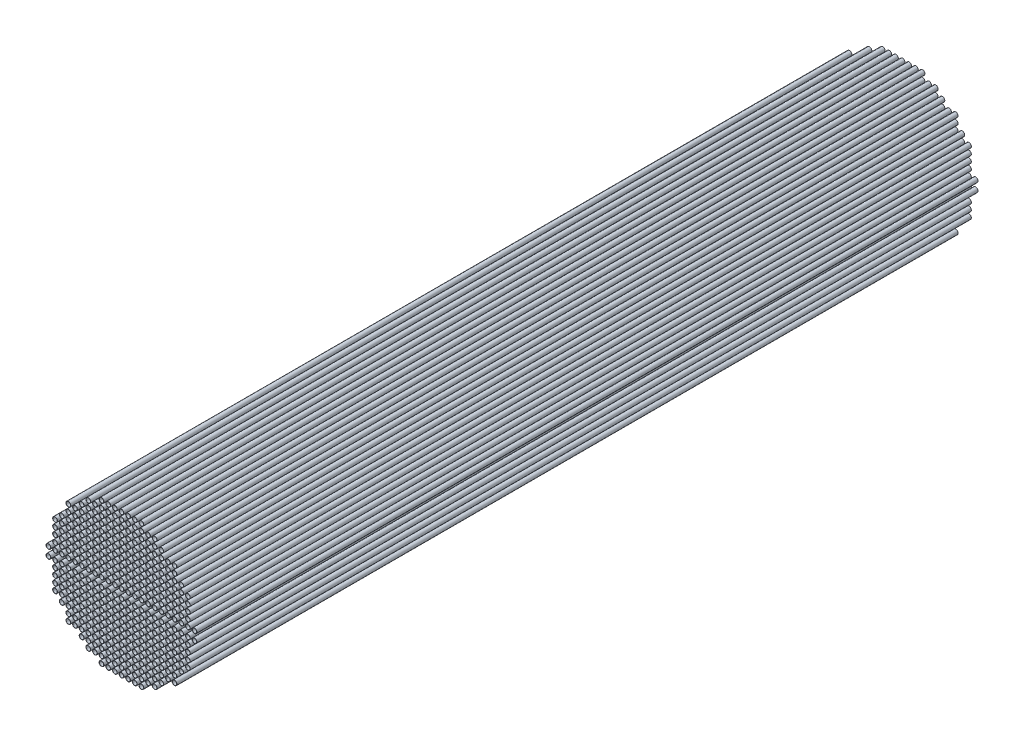
SolidWorks part; units mm, degrees
ref_plane "Plano frontal" through (0, 0, 0) normal (0, 0, 1) x (1, 0, 0)
ref_plane "Plano superior" through (0, 0, 0) normal (0, 1, 0) x (1, 0, 0)
ref_plane "Plano direito" through (0, 0, 0) normal (1, 0, 0) x (0, 0, -1)
sketch "Sketch2" plane through (0, 0, 0) normal (0, 0, 1) x (1, 0, 0)
  line L0 (-740, -13.1986) -> (-1154.1586, -13.1986) construction
  circle A0 centre (-454, -30.1144) radius 9.4918
  circle A1 centre (-454, -30.1144) radius 8.4918
  circle A2 centre (-480, -30.1144) radius 9.4918
  circle A3 centre (-480, -30.1144) radius 8.4918
  circle A4 centre (-506, -30.1144) radius 9.4918
  circle A5 centre (-506, -30.1144) radius 8.4918
  circle A6 centre (-532, -30.1144) radius 9.4918
  circle A7 centre (-532, -30.1144) radius 8.4918
  circle A8 centre (-558, -30.1144) radius 9.4918
  circle A9 centre (-558, -30.1144) radius 8.4918
  circle A10 centre (-584, -30.1144) radius 9.4918
  circle A11 centre (-584, -30.1144) radius 8.4918
  circle A12 centre (-610, -30.1144) radius 9.4918
  circle A13 centre (-610, -30.1144) radius 8.4918
  circle A14 centre (-636, -30.1144) radius 9.4918
  circle A15 centre (-636, -30.1144) radius 8.4918
  circle A16 centre (-662, -30.1144) radius 9.4918
  circle A17 centre (-662, -30.1144) radius 8.4918
  circle A18 centre (-688, -30.1144) radius 9.4918
  circle A19 centre (-688, -30.1144) radius 8.4918
  circle A20 centre (-714, -30.1144) radius 9.4918
  circle A21 centre (-714, -30.1144) radius 8.4918
  circle A22 centre (-740, -30.1144) radius 9.4918
  circle A23 centre (-740, -30.1144) radius 8.4918
  circle A24 centre (-766, -30.1144) radius 9.4918
  circle A25 centre (-766, -30.1144) radius 8.4918
  circle A26 centre (-792, -30.1144) radius 9.4918
  circle A27 centre (-792, -30.1144) radius 8.4918
  circle A28 centre (-818, -30.1144) radius 9.4918
  circle A29 centre (-818, -30.1144) radius 8.4918
  circle A30 centre (-844, -30.1144) radius 9.4918
  circle A31 centre (-844, -30.1144) radius 8.4918
  circle A32 centre (-870, -30.1144) radius 9.4918
  circle A33 centre (-870, -30.1144) radius 8.4918
  circle A34 centre (-896, -30.1144) radius 9.4918
  circle A35 centre (-896, -30.1144) radius 8.4918
  circle A36 centre (-922, -30.1144) radius 9.4918
  circle A37 centre (-922, -30.1144) radius 8.4918
  circle A38 centre (-948, -30.1144) radius 9.4918
  circle A39 centre (-948, -30.1144) radius 8.4918
  circle A40 centre (-974, -30.1144) radius 9.4918
  circle A41 centre (-974, -30.1144) radius 8.4918
  circle A42 centre (-1000, -30.1144) radius 9.4918
  circle A43 centre (-1000, -30.1144) radius 8.4918
  circle A44 centre (-1026, -30.1144) radius 9.4918
  circle A45 centre (-1026, -30.1144) radius 8.4918
  circle A46 centre (-480, -56.1144) radius 9.4918
  circle A47 centre (-480, -56.1144) radius 8.4918
  circle A48 centre (-506, -56.1144) radius 9.4918
  circle A49 centre (-506, -56.1144) radius 8.4918
  circle A50 centre (-532, -56.1144) radius 9.4918
  circle A51 centre (-532, -56.1144) radius 8.4918
  circle A52 centre (-558, -56.1144) radius 9.4918
  circle A53 centre (-558, -56.1144) radius 8.4918
  circle A54 centre (-584, -56.1144) radius 9.4918
  circle A55 centre (-584, -56.1144) radius 8.4918
  circle A56 centre (-610, -56.1144) radius 9.4918
  circle A57 centre (-610, -56.1144) radius 8.4918
  circle A58 centre (-636, -56.1144) radius 9.4918
  circle A59 centre (-636, -56.1144) radius 8.4918
  circle A60 centre (-662, -56.1144) radius 9.4918
  circle A61 centre (-662, -56.1144) radius 8.4918
  circle A62 centre (-688, -56.1144) radius 9.4918
  circle A63 centre (-688, -56.1144) radius 8.4918
  circle A64 centre (-714, -56.1144) radius 9.4918
  circle A65 centre (-714, -56.1144) radius 8.4918
  circle A66 centre (-740, -56.1144) radius 9.4918
  circle A67 centre (-740, -56.1144) radius 8.4918
  circle A68 centre (-766, -56.1144) radius 9.4918
  circle A69 centre (-766, -56.1144) radius 8.4918
  circle A70 centre (-792, -56.1144) radius 9.4918
  circle A71 centre (-792, -56.1144) radius 8.4918
  circle A72 centre (-818, -56.1144) radius 9.4918
  circle A73 centre (-818, -56.1144) radius 8.4918
  circle A74 centre (-844, -56.1144) radius 9.4918
  circle A75 centre (-844, -56.1144) radius 8.4918
  circle A76 centre (-870, -56.1144) radius 9.4918
  circle A77 centre (-870, -56.1144) radius 8.4918
  circle A78 centre (-896, -56.1144) radius 9.4918
  circle A79 centre (-896, -56.1144) radius 8.4918
  circle A80 centre (-922, -56.1144) radius 9.4918
  circle A81 centre (-922, -56.1144) radius 8.4918
  circle A82 centre (-948, -56.1144) radius 9.4918
  circle A83 centre (-948, -56.1144) radius 8.4918
  circle A84 centre (-974, -56.1144) radius 9.4918
  circle A85 centre (-974, -56.1144) radius 8.4918
  circle A86 centre (-1000, -56.1144) radius 9.4918
  circle A87 centre (-1000, -56.1144) radius 8.4918
  circle A88 centre (-818, 263.7171) radius 8.4918
  circle A89 centre (-818, 263.7171) radius 9.4918
  circle A90 centre (-480, -82.1144) radius 9.4918
  circle A91 centre (-480, -82.1144) radius 8.4918
  circle A92 centre (-506, -82.1144) radius 9.4918
  circle A93 centre (-506, -82.1144) radius 8.4918
  circle A94 centre (-532, -82.1144) radius 9.4918
  circle A95 centre (-532, -82.1144) radius 8.4918
  circle A96 centre (-558, -82.1144) radius 9.4918
  circle A97 centre (-558, -82.1144) radius 8.4918
  circle A98 centre (-584, -82.1144) radius 9.4918
  circle A99 centre (-584, -82.1144) radius 8.4918
  circle A100 centre (-610, -82.1144) radius 9.4918
  circle A101 centre (-610, -82.1144) radius 8.4918
  circle A102 centre (-636, -82.1144) radius 9.4918
  circle A103 centre (-636, -82.1144) radius 8.4918
  circle A104 centre (-662, -82.1144) radius 9.4918
  circle A105 centre (-662, -82.1144) radius 8.4918
  circle A106 centre (-688, -82.1144) radius 9.4918
  circle A107 centre (-688, -82.1144) radius 8.4918
  circle A108 centre (-714, -82.1144) radius 9.4918
  circle A109 centre (-714, -82.1144) radius 8.4918
  circle A110 centre (-740, -82.1144) radius 9.4918
  circle A111 centre (-740, -82.1144) radius 8.4918
  circle A112 centre (-766, -82.1144) radius 9.4918
  circle A113 centre (-766, -82.1144) radius 8.4918
  circle A114 centre (-792, -82.1144) radius 9.4918
  circle A115 centre (-792, -82.1144) radius 8.4918
  circle A116 centre (-818, -82.1144) radius 9.4918
  circle A117 centre (-818, -82.1144) radius 8.4918
  circle A118 centre (-844, -82.1144) radius 9.4918
  circle A119 centre (-844, -82.1144) radius 8.4918
  circle A120 centre (-870, -82.1144) radius 9.4918
  circle A121 centre (-870, -82.1144) radius 8.4918
  circle A122 centre (-896, -82.1144) radius 9.4918
  circle A123 centre (-896, -82.1144) radius 8.4918
  circle A124 centre (-922, -82.1144) radius 9.4918
  circle A125 centre (-922, -82.1144) radius 8.4918
  circle A126 centre (-948, -82.1144) radius 9.4918
  circle A127 centre (-948, -82.1144) radius 8.4918
  circle A128 centre (-974, -82.1144) radius 9.4918
  circle A129 centre (-974, -82.1144) radius 8.4918
  circle A130 centre (-1000, -82.1144) radius 9.4918
  circle A131 centre (-1000, -82.1144) radius 8.4918
  circle A132 centre (-792, 263.7171) radius 8.4918
  circle A133 centre (-792, 263.7171) radius 9.4918
  circle A134 centre (-480, -108.1144) radius 9.4918
  circle A135 centre (-480, -108.1144) radius 8.4918
  circle A136 centre (-506, -108.1144) radius 9.4918
  circle A137 centre (-506, -108.1144) radius 8.4918
  circle A138 centre (-532, -108.1144) radius 9.4918
  circle A139 centre (-532, -108.1144) radius 8.4918
  circle A140 centre (-558, -108.1144) radius 9.4918
  circle A141 centre (-558, -108.1144) radius 8.4918
  circle A142 centre (-584, -108.1144) radius 9.4918
  circle A143 centre (-584, -108.1144) radius 8.4918
  circle A144 centre (-610, -108.1144) radius 9.4918
  circle A145 centre (-610, -108.1144) radius 8.4918
  circle A146 centre (-636, -108.1144) radius 9.4918
  circle A147 centre (-636, -108.1144) radius 8.4918
  circle A148 centre (-662, -108.1144) radius 9.4918
  circle A149 centre (-662, -108.1144) radius 8.4918
  circle A150 centre (-688, -108.1144) radius 9.4918
  circle A151 centre (-688, -108.1144) radius 8.4918
  circle A152 centre (-714, -108.1144) radius 9.4918
  circle A153 centre (-714, -108.1144) radius 8.4918
  circle A154 centre (-740, -108.1144) radius 9.4918
  circle A155 centre (-740, -108.1144) radius 8.4918
  circle A156 centre (-766, -108.1144) radius 9.4918
  circle A157 centre (-766, -108.1144) radius 8.4918
  circle A158 centre (-792, -108.1144) radius 9.4918
  circle A159 centre (-792, -108.1144) radius 8.4918
  circle A160 centre (-818, -108.1144) radius 9.4918
  circle A161 centre (-818, -108.1144) radius 8.4918
  circle A162 centre (-844, -108.1144) radius 9.4918
  circle A163 centre (-844, -108.1144) radius 8.4918
  circle A164 centre (-870, -108.1144) radius 9.4918
  circle A165 centre (-870, -108.1144) radius 8.4918
  circle A166 centre (-896, -108.1144) radius 9.4918
  circle A167 centre (-896, -108.1144) radius 8.4918
  circle A168 centre (-922, -108.1144) radius 9.4918
  circle A169 centre (-922, -108.1144) radius 8.4918
  circle A170 centre (-948, -108.1144) radius 9.4918
  circle A171 centre (-948, -108.1144) radius 8.4918
  circle A172 centre (-974, -108.1144) radius 9.4918
  circle A173 centre (-974, -108.1144) radius 8.4918
  circle A174 centre (-1000, -108.1144) radius 9.4918
  circle A175 centre (-1000, -108.1144) radius 8.4918
  circle A176 centre (-766, 263.7171) radius 8.4918
  circle A177 centre (-766, 263.7171) radius 9.4918
  circle A178 centre (-480, -134.1144) radius 9.4918
  circle A179 centre (-480, -134.1144) radius 8.4918
  circle A180 centre (-506, -134.1144) radius 9.4918
  circle A181 centre (-506, -134.1144) radius 8.4918
  circle A182 centre (-532, -134.1144) radius 9.4918
  circle A183 centre (-532, -134.1144) radius 8.4918
  circle A184 centre (-558, -134.1144) radius 9.4918
  circle A185 centre (-558, -134.1144) radius 8.4918
  circle A186 centre (-584, -134.1144) radius 9.4918
  circle A187 centre (-584, -134.1144) radius 8.4918
  circle A188 centre (-610, -134.1144) radius 9.4918
  circle A189 centre (-610, -134.1144) radius 8.4918
  circle A190 centre (-636, -134.1144) radius 9.4918
  circle A191 centre (-636, -134.1144) radius 8.4918
  circle A192 centre (-662, -134.1144) radius 9.4918
  circle A193 centre (-662, -134.1144) radius 8.4918
  circle A194 centre (-688, -134.1144) radius 9.4918
  circle A195 centre (-688, -134.1144) radius 8.4918
  circle A196 centre (-714, -134.1144) radius 9.4918
  circle A197 centre (-714, -134.1144) radius 8.4918
  circle A198 centre (-740, -134.1144) radius 9.4918
  circle A199 centre (-740, -134.1144) radius 8.4918
  circle A200 centre (-766, -134.1144) radius 9.4918
  circle A201 centre (-766, -134.1144) radius 8.4918
  circle A202 centre (-792, -134.1144) radius 9.4918
  circle A203 centre (-792, -134.1144) radius 8.4918
  circle A204 centre (-818, -134.1144) radius 9.4918
  circle A205 centre (-818, -134.1144) radius 8.4918
  circle A206 centre (-844, -134.1144) radius 9.4918
  circle A207 centre (-844, -134.1144) radius 8.4918
  circle A208 centre (-870, -134.1144) radius 9.4918
  circle A209 centre (-870, -134.1144) radius 8.4918
  circle A210 centre (-896, -134.1144) radius 9.4918
  circle A211 centre (-896, -134.1144) radius 8.4918
  circle A212 centre (-922, -134.1144) radius 9.4918
  circle A213 centre (-922, -134.1144) radius 8.4918
  circle A214 centre (-948, -134.1144) radius 9.4918
  circle A215 centre (-948, -134.1144) radius 8.4918
  circle A216 centre (-974, -134.1144) radius 9.4918
  circle A217 centre (-974, -134.1144) radius 8.4918
  circle A218 centre (-1000, -134.1144) radius 9.4918
  circle A219 centre (-1000, -134.1144) radius 8.4918
  circle A220 centre (-740, 263.7171) radius 8.4918
  circle A221 centre (-740, 263.7171) radius 9.4918
  circle A222 centre (-714, 263.7171) radius 8.4918
  circle A223 centre (-714, 263.7171) radius 9.4918
  circle A224 centre (-506, -160.1144) radius 9.4918
  circle A225 centre (-506, -160.1144) radius 8.4918
  circle A226 centre (-532, -160.1144) radius 9.4918
  circle A227 centre (-532, -160.1144) radius 8.4918
  circle A228 centre (-558, -160.1144) radius 9.4918
  circle A229 centre (-558, -160.1144) radius 8.4918
  circle A230 centre (-584, -160.1144) radius 9.4918
  circle A231 centre (-584, -160.1144) radius 8.4918
  circle A232 centre (-610, -160.1144) radius 9.4918
  circle A233 centre (-610, -160.1144) radius 8.4918
  circle A234 centre (-636, -160.1144) radius 9.4918
  circle A235 centre (-636, -160.1144) radius 8.4918
  circle A236 centre (-662, -160.1144) radius 9.4918
  circle A237 centre (-662, -160.1144) radius 8.4918
  circle A238 centre (-688, -160.1144) radius 9.4918
  circle A239 centre (-688, -160.1144) radius 8.4918
  circle A240 centre (-714, -160.1144) radius 9.4918
  circle A241 centre (-714, -160.1144) radius 8.4918
  circle A242 centre (-740, -160.1144) radius 9.4918
  circle A243 centre (-740, -160.1144) radius 8.4918
  circle A244 centre (-766, -160.1144) radius 9.4918
  circle A245 centre (-766, -160.1144) radius 8.4918
  circle A246 centre (-792, -160.1144) radius 9.4918
  circle A247 centre (-792, -160.1144) radius 8.4918
  circle A248 centre (-818, -160.1144) radius 9.4918
  circle A249 centre (-818, -160.1144) radius 8.4918
  circle A250 centre (-844, -160.1144) radius 9.4918
  circle A251 centre (-844, -160.1144) radius 8.4918
  circle A252 centre (-870, -160.1144) radius 9.4918
  circle A253 centre (-870, -160.1144) radius 8.4918
  circle A254 centre (-896, -160.1144) radius 9.4918
  circle A255 centre (-896, -160.1144) radius 8.4918
  circle A256 centre (-922, -160.1144) radius 9.4918
  circle A257 centre (-922, -160.1144) radius 8.4918
  circle A258 centre (-948, -160.1144) radius 9.4918
  circle A259 centre (-948, -160.1144) radius 8.4918
  circle A260 centre (-974, -160.1144) radius 9.4918
  circle A261 centre (-974, -160.1144) radius 8.4918
  circle A262 centre (-688, 263.7171) radius 8.4918
  circle A263 centre (-688, 263.7171) radius 9.4918
  circle A264 centre (-662, 263.7171) radius 8.4918
  circle A265 centre (-662, 263.7171) radius 9.4918
  circle A266 centre (-870, 237.7171) radius 8.4918
  circle A267 centre (-870, 237.7171) radius 9.4918
  circle A268 centre (-844, 237.7171) radius 8.4918
  circle A269 centre (-844, 237.7171) radius 9.4918
  circle A270 centre (-532, -186.1144) radius 9.4918
  circle A271 centre (-532, -186.1144) radius 8.4918
  circle A272 centre (-558, -186.1144) radius 9.4918
  circle A273 centre (-558, -186.1144) radius 8.4918
  circle A274 centre (-584, -186.1144) radius 9.4918
  circle A275 centre (-584, -186.1144) radius 8.4918
  circle A276 centre (-610, -186.1144) radius 9.4918
  circle A277 centre (-610, -186.1144) radius 8.4918
  circle A278 centre (-636, -186.1144) radius 9.4918
  circle A279 centre (-636, -186.1144) radius 8.4918
  circle A280 centre (-662, -186.1144) radius 9.4918
  circle A281 centre (-662, -186.1144) radius 8.4918
  circle A282 centre (-688, -186.1144) radius 9.4918
  circle A283 centre (-688, -186.1144) radius 8.4918
  circle A284 centre (-714, -186.1144) radius 9.4918
  circle A285 centre (-714, -186.1144) radius 8.4918
  circle A286 centre (-740, -186.1144) radius 9.4918
  circle A287 centre (-740, -186.1144) radius 8.4918
  circle A288 centre (-766, -186.1144) radius 9.4918
  circle A289 centre (-766, -186.1144) radius 8.4918
  circle A290 centre (-792, -186.1144) radius 9.4918
  circle A291 centre (-792, -186.1144) radius 8.4918
  circle A292 centre (-818, -186.1144) radius 9.4918
  circle A293 centre (-818, -186.1144) radius 8.4918
  circle A294 centre (-844, -186.1144) radius 9.4918
  circle A295 centre (-844, -186.1144) radius 8.4918
  circle A296 centre (-870, -186.1144) radius 9.4918
  circle A297 centre (-870, -186.1144) radius 8.4918
  circle A298 centre (-896, -186.1144) radius 9.4918
  circle A299 centre (-896, -186.1144) radius 8.4918
  circle A300 centre (-922, -186.1144) radius 9.4918
  circle A301 centre (-922, -186.1144) radius 8.4918
  circle A302 centre (-948, -186.1144) radius 9.4918
  circle A303 centre (-948, -186.1144) radius 8.4918
  circle A304 centre (-818, 237.7171) radius 8.4918
  circle A305 centre (-818, 237.7171) radius 9.4918
  circle A306 centre (-792, 237.7171) radius 8.4918
  circle A307 centre (-792, 237.7171) radius 9.4918
  circle A308 centre (-766, 237.7171) radius 8.4918
  circle A309 centre (-766, 237.7171) radius 9.4918
  circle A310 centre (-740, 237.7171) radius 8.4918
  circle A311 centre (-740, 237.7171) radius 9.4918
  circle A312 centre (-714, 237.7171) radius 8.4918
  circle A313 centre (-714, 237.7171) radius 9.4918
  circle A314 centre (-532, -212.1144) radius 9.4918
  circle A315 centre (-532, -212.1144) radius 8.4918
  circle A316 centre (-558, -212.1144) radius 9.4918
  circle A317 centre (-558, -212.1144) radius 8.4918
  circle A318 centre (-584, -212.1144) radius 9.4918
  circle A319 centre (-584, -212.1144) radius 8.4918
  circle A320 centre (-610, -212.1144) radius 9.4918
  circle A321 centre (-610, -212.1144) radius 8.4918
  circle A322 centre (-636, -212.1144) radius 9.4918
  circle A323 centre (-636, -212.1144) radius 8.4918
  circle A324 centre (-662, -212.1144) radius 9.4918
  circle A325 centre (-662, -212.1144) radius 8.4918
  circle A326 centre (-688, -212.1144) radius 9.4918
  circle A327 centre (-688, -212.1144) radius 8.4918
  circle A328 centre (-714, -212.1144) radius 9.4918
  circle A329 centre (-714, -212.1144) radius 8.4918
  circle A330 centre (-740, -212.1144) radius 9.4918
  circle A331 centre (-740, -212.1144) radius 8.4918
  circle A332 centre (-766, -212.1144) radius 9.4918
  circle A333 centre (-766, -212.1144) radius 8.4918
  circle A334 centre (-792, -212.1144) radius 9.4918
  circle A335 centre (-792, -212.1144) radius 8.4918
  circle A336 centre (-818, -212.1144) radius 9.4918
  circle A337 centre (-818, -212.1144) radius 8.4918
  circle A338 centre (-844, -212.1144) radius 9.4918
  circle A339 centre (-844, -212.1144) radius 8.4918
  circle A340 centre (-870, -212.1144) radius 9.4918
  circle A341 centre (-870, -212.1144) radius 8.4918
  circle A342 centre (-896, -212.1144) radius 9.4918
  circle A343 centre (-896, -212.1144) radius 8.4918
  circle A344 centre (-922, -212.1144) radius 9.4918
  circle A345 centre (-922, -212.1144) radius 8.4918
  circle A346 centre (-948, -212.1144) radius 9.4918
  circle A347 centre (-948, -212.1144) radius 8.4918
  circle A348 centre (-688, 237.7171) radius 8.4918
  circle A349 centre (-688, 237.7171) radius 9.4918
  circle A350 centre (-662, 237.7171) radius 8.4918
  circle A351 centre (-662, 237.7171) radius 9.4918
  circle A352 centre (-636, 237.7171) radius 8.4918
  circle A353 centre (-636, 237.7171) radius 9.4918
  circle A354 centre (-610, 237.7171) radius 8.4918
  circle A355 centre (-610, 237.7171) radius 9.4918
  circle A356 centre (-896, 211.7171) radius 8.4918
  circle A357 centre (-896, 211.7171) radius 9.4918
  circle A358 centre (-870, 211.7171) radius 8.4918
  circle A359 centre (-870, 211.7171) radius 9.4918
  circle A360 centre (-844, 211.7171) radius 8.4918
  circle A361 centre (-844, 211.7171) radius 9.4918
  circle A362 centre (-584, -238.1144) radius 9.4918
  circle A363 centre (-584, -238.1144) radius 8.4918
  circle A364 centre (-610, -238.1144) radius 9.4918
  circle A365 centre (-610, -238.1144) radius 8.4918
  circle A366 centre (-636, -238.1144) radius 9.4918
  circle A367 centre (-636, -238.1144) radius 8.4918
  circle A368 centre (-662, -238.1144) radius 9.4918
  circle A369 centre (-662, -238.1144) radius 8.4918
  circle A370 centre (-688, -238.1144) radius 9.4918
  circle A371 centre (-688, -238.1144) radius 8.4918
  circle A372 centre (-714, -238.1144) radius 9.4918
  circle A373 centre (-714, -238.1144) radius 8.4918
  circle A374 centre (-740, -238.1144) radius 9.4918
  circle A375 centre (-740, -238.1144) radius 8.4918
  circle A376 centre (-766, -238.1144) radius 9.4918
  circle A377 centre (-766, -238.1144) radius 8.4918
  circle A378 centre (-792, -238.1144) radius 9.4918
  circle A379 centre (-792, -238.1144) radius 8.4918
  circle A380 centre (-818, -238.1144) radius 9.4918
  circle A381 centre (-818, -238.1144) radius 8.4918
  circle A382 centre (-844, -238.1144) radius 9.4918
  circle A383 centre (-844, -238.1144) radius 8.4918
  circle A384 centre (-870, -238.1144) radius 9.4918
  circle A385 centre (-870, -238.1144) radius 8.4918
  circle A386 centre (-896, -238.1144) radius 9.4918
  circle A387 centre (-896, -238.1144) radius 8.4918
  circle A388 centre (-818, 211.7171) radius 8.4918
  circle A389 centre (-818, 211.7171) radius 9.4918
  circle A390 centre (-792, 211.7171) radius 8.4918
  circle A391 centre (-792, 211.7171) radius 9.4918
  circle A392 centre (-766, 211.7171) radius 8.4918
  circle A393 centre (-766, 211.7171) radius 9.4918
  circle A394 centre (-740, 211.7171) radius 8.4918
  circle A395 centre (-740, 211.7171) radius 9.4918
  circle A396 centre (-714, 211.7171) radius 8.4918
  circle A397 centre (-714, 211.7171) radius 9.4918
  circle A398 centre (-688, 211.7171) radius 8.4918
  circle A399 centre (-688, 211.7171) radius 9.4918
  circle A400 centre (-662, 211.7171) radius 8.4918
  circle A401 centre (-662, 211.7171) radius 9.4918
  circle A402 centre (-636, 211.7171) radius 8.4918
  circle A403 centre (-636, 211.7171) radius 9.4918
  circle A404 centre (-610, 211.7171) radius 8.4918
  circle A405 centre (-610, 211.7171) radius 9.4918
  circle A406 centre (-584, 211.7171) radius 8.4918
  circle A407 centre (-584, 211.7171) radius 9.4918
  circle A408 centre (-610, -264.1144) radius 9.4918
  circle A409 centre (-610, -264.1144) radius 8.4918
  circle A410 centre (-636, -264.1144) radius 9.4918
  circle A411 centre (-636, -264.1144) radius 8.4918
  circle A412 centre (-662, -264.1144) radius 9.4918
  circle A413 centre (-662, -264.1144) radius 8.4918
  circle A414 centre (-688, -264.1144) radius 9.4918
  circle A415 centre (-688, -264.1144) radius 8.4918
  circle A416 centre (-714, -264.1144) radius 9.4918
  circle A417 centre (-714, -264.1144) radius 8.4918
  circle A418 centre (-740, -264.1144) radius 9.4918
  circle A419 centre (-740, -264.1144) radius 8.4918
  circle A420 centre (-766, -264.1144) radius 9.4918
  circle A421 centre (-766, -264.1144) radius 8.4918
  circle A422 centre (-792, -264.1144) radius 9.4918
  circle A423 centre (-792, -264.1144) radius 8.4918
  circle A424 centre (-818, -264.1144) radius 9.4918
  circle A425 centre (-818, -264.1144) radius 8.4918
  circle A426 centre (-844, -264.1144) radius 9.4918
  circle A427 centre (-844, -264.1144) radius 8.4918
  circle A428 centre (-870, -264.1144) radius 9.4918
  circle A429 centre (-870, -264.1144) radius 8.4918
  circle A430 centre (-948, 185.7171) radius 8.4918
  circle A431 centre (-948, 185.7171) radius 9.4918
  circle A432 centre (-922, 185.7171) radius 8.4918
  circle A433 centre (-922, 185.7171) radius 9.4918
  circle A434 centre (-896, 185.7171) radius 8.4918
  circle A435 centre (-896, 185.7171) radius 9.4918
  circle A436 centre (-870, 185.7171) radius 8.4918
  circle A437 centre (-870, 185.7171) radius 9.4918
  circle A438 centre (-844, 185.7171) radius 8.4918
  circle A439 centre (-844, 185.7171) radius 9.4918
  circle A440 centre (-818, 185.7171) radius 8.4918
  circle A441 centre (-818, 185.7171) radius 9.4918
  circle A442 centre (-792, 185.7171) radius 8.4918
  circle A443 centre (-792, 185.7171) radius 9.4918
  circle A444 centre (-766, 185.7171) radius 8.4918
  circle A445 centre (-766, 185.7171) radius 9.4918
  circle A446 centre (-740, 185.7171) radius 8.4918
  circle A447 centre (-740, 185.7171) radius 9.4918
  circle A448 centre (-714, 185.7171) radius 8.4918
  circle A449 centre (-714, 185.7171) radius 9.4918
  circle A450 centre (-688, 185.7171) radius 8.4918
  circle A451 centre (-688, 185.7171) radius 9.4918
  circle A452 centre (-662, 185.7171) radius 8.4918
  circle A453 centre (-662, 185.7171) radius 9.4918
  circle A454 centre (-636, 185.7171) radius 8.4918
  circle A455 centre (-636, 185.7171) radius 9.4918
  circle A456 centre (-662, -290.1144) radius 9.4918
  circle A457 centre (-662, -290.1144) radius 8.4918
  circle A458 centre (-688, -290.1144) radius 9.4918
  circle A459 centre (-688, -290.1144) radius 8.4918
  circle A460 centre (-714, -290.1144) radius 9.4918
  circle A461 centre (-714, -290.1144) radius 8.4918
  circle A462 centre (-740, -290.1144) radius 9.4918
  circle A463 centre (-740, -290.1144) radius 8.4918
  circle A464 centre (-766, -290.1144) radius 9.4918
  circle A465 centre (-766, -290.1144) radius 8.4918
  circle A466 centre (-792, -290.1144) radius 9.4918
  circle A467 centre (-792, -290.1144) radius 8.4918
  circle A468 centre (-818, -290.1144) radius 9.4918
  circle A469 centre (-818, -290.1144) radius 8.4918
  circle A470 centre (-610, 185.7171) radius 8.4918
  circle A471 centre (-610, 185.7171) radius 9.4918
  circle A472 centre (-584, 185.7171) radius 8.4918
  circle A473 centre (-584, 185.7171) radius 9.4918
  circle A474 centre (-558, 185.7171) radius 8.4918
  circle A475 centre (-558, 185.7171) radius 9.4918
  circle A476 centre (-532, 185.7171) radius 8.4918
  circle A477 centre (-532, 185.7171) radius 9.4918
  circle A478 centre (-948, 159.7171) radius 8.4918
  circle A479 centre (-948, 159.7171) radius 9.4918
  circle A480 centre (-922, 159.7171) radius 8.4918
  circle A481 centre (-922, 159.7171) radius 9.4918
  circle A482 centre (-896, 159.7171) radius 8.4918
  circle A483 centre (-896, 159.7171) radius 9.4918
  circle A484 centre (-870, 159.7171) radius 8.4918
  circle A485 centre (-870, 159.7171) radius 9.4918
  circle A486 centre (-844, 159.7171) radius 8.4918
  circle A487 centre (-844, 159.7171) radius 9.4918
  circle A488 centre (-818, 159.7171) radius 8.4918
  circle A489 centre (-818, 159.7171) radius 9.4918
  circle A490 centre (-792, 159.7171) radius 8.4918
  circle A491 centre (-792, 159.7171) radius 9.4918
  circle A492 centre (-766, 159.7171) radius 8.4918
  circle A493 centre (-766, 159.7171) radius 9.4918
  circle A494 centre (-740, 159.7171) radius 8.4918
  circle A495 centre (-740, 159.7171) radius 9.4918
  circle A496 centre (-714, 159.7171) radius 8.4918
  circle A497 centre (-714, 159.7171) radius 9.4918
  circle A498 centre (-688, 159.7171) radius 8.4918
  circle A499 centre (-688, 159.7171) radius 9.4918
  circle A500 centre (-662, 159.7171) radius 8.4918
  circle A501 centre (-662, 159.7171) radius 9.4918
  circle A502 centre (-636, 159.7171) radius 8.4918
  circle A503 centre (-636, 159.7171) radius 9.4918
  circle A504 centre (-610, 159.7171) radius 8.4918
  circle A505 centre (-610, 159.7171) radius 9.4918
  circle A506 centre (-896, -290.1144) radius 9.4918 [skipped]
  circle A507 centre (-896, -290.1144) radius 8.4918 [skipped]
  circle A508 centre (-922, -290.1144) radius 9.4918 [skipped]
  circle A509 centre (-922, -290.1144) radius 8.4918 [skipped]
  circle A510 centre (-948, -290.1144) radius 9.4918 [skipped]
  circle A511 centre (-948, -290.1144) radius 8.4918 [skipped]
  circle A512 centre (-974, -290.1144) radius 9.4918 [skipped]
  circle A513 centre (-974, -290.1144) radius 8.4918 [skipped]
  circle A514 centre (-1000, -290.1144) radius 9.4918 [skipped]
  circle A515 centre (-1000, -290.1144) radius 8.4918 [skipped]
  circle A516 centre (-1026, -290.1144) radius 9.4918 [skipped]
  circle A517 centre (-1026, -290.1144) radius 8.4918 [skipped]
  circle A518 centre (-844, -290.1144) radius 9.4918 [skipped]
  circle A519 centre (-844, -290.1144) radius 8.4918 [skipped]
  circle A520 centre (-870, -290.1144) radius 9.4918 [skipped]
  circle A521 centre (-870, -290.1144) radius 8.4918 [skipped]
  circle A522 centre (-896, -264.1144) radius 9.4918 [skipped]
  circle A523 centre (-896, -264.1144) radius 8.4918 [skipped]
  circle A524 centre (-922, -264.1144) radius 9.4918 [skipped]
  circle A525 centre (-922, -264.1144) radius 8.4918 [skipped]
  circle A526 centre (-948, -264.1144) radius 9.4918 [skipped]
  circle A527 centre (-948, -264.1144) radius 8.4918 [skipped]
  circle A528 centre (-974, -264.1144) radius 9.4918 [skipped]
  circle A529 centre (-974, -264.1144) radius 8.4918 [skipped]
  circle A530 centre (-1000, -264.1144) radius 9.4918 [skipped]
  circle A531 centre (-1000, -264.1144) radius 8.4918 [skipped]
  circle A532 centre (-1026, -264.1144) radius 9.4918 [skipped]
  circle A533 centre (-1026, -264.1144) radius 8.4918 [skipped]
  circle A534 centre (-922, -238.1144) radius 9.4918 [skipped]
  circle A535 centre (-922, -238.1144) radius 8.4918 [skipped]
  circle A536 centre (-948, -238.1144) radius 9.4918 [skipped]
  circle A537 centre (-948, -238.1144) radius 8.4918 [skipped]
  circle A538 centre (-974, -238.1144) radius 9.4918 [skipped]
  circle A539 centre (-974, -238.1144) radius 8.4918 [skipped]
  circle A540 centre (-1000, -238.1144) radius 9.4918 [skipped]
  circle A541 centre (-1000, -238.1144) radius 8.4918 [skipped]
  circle A542 centre (-1026, -238.1144) radius 9.4918 [skipped]
  circle A543 centre (-1026, -238.1144) radius 8.4918 [skipped]
  circle A544 centre (-974, -186.1144) radius 9.4918 [skipped]
  circle A545 centre (-974, -186.1144) radius 8.4918 [skipped]
  circle A546 centre (-1000, -186.1144) radius 9.4918 [skipped]
  circle A547 centre (-1000, -186.1144) radius 8.4918 [skipped]
  circle A548 centre (-1026, -186.1144) radius 9.4918 [skipped]
  circle A549 centre (-1026, -186.1144) radius 8.4918 [skipped]
  circle A550 centre (-974, -212.1144) radius 9.4918 [skipped]
  circle A551 centre (-974, -212.1144) radius 8.4918 [skipped]
  circle A552 centre (-1000, -212.1144) radius 9.4918 [skipped]
  circle A553 centre (-1000, -212.1144) radius 8.4918 [skipped]
  circle A554 centre (-1026, -212.1144) radius 9.4918 [skipped]
  circle A555 centre (-1026, -212.1144) radius 8.4918 [skipped]
  circle A556 centre (-1000, -160.1144) radius 9.4918 [skipped]
  circle A557 centre (-1000, -160.1144) radius 8.4918 [skipped]
  circle A558 centre (-1026, -160.1144) radius 9.4918 [skipped]
  circle A559 centre (-1026, -160.1144) radius 8.4918 [skipped]
  circle A560 centre (-1026, -56.1144) radius 9.4918 [skipped]
  circle A561 centre (-1026, -56.1144) radius 8.4918 [skipped]
  circle A562 centre (-1026, -82.1144) radius 9.4918 [skipped]
  circle A563 centre (-1026, -82.1144) radius 8.4918 [skipped]
  circle A564 centre (-1026, -108.1144) radius 9.4918 [skipped]
  circle A565 centre (-1026, -108.1144) radius 8.4918 [skipped]
  circle A566 centre (-1026, -134.1144) radius 9.4918 [skipped]
  circle A567 centre (-1026, -134.1144) radius 8.4918 [skipped]
  circle A568 centre (-480, -160.1144) radius 9.4918 [skipped]
  circle A569 centre (-480, -160.1144) radius 8.4918 [skipped]
  circle A570 centre (-480, -186.1144) radius 9.4918 [skipped]
  circle A571 centre (-480, -186.1144) radius 8.4918 [skipped]
  circle A572 centre (-480, -212.1144) radius 9.4918 [skipped]
  circle A573 centre (-480, -212.1144) radius 8.4918 [skipped]
  circle A574 centre (-480, -238.1144) radius 9.4918 [skipped]
  circle A575 centre (-480, -238.1144) radius 8.4918 [skipped]
  circle A576 centre (-480, -264.1144) radius 9.4918 [skipped]
  circle A577 centre (-480, -264.1144) radius 8.4918 [skipped]
  circle A578 centre (-480, -290.1144) radius 9.4918 [skipped]
  circle A579 centre (-480, -290.1144) radius 8.4918 [skipped]
  circle A580 centre (-454, -160.1144) radius 9.4918 [skipped]
  circle A581 centre (-454, -160.1144) radius 8.4918 [skipped]
  circle A582 centre (-454, -186.1144) radius 9.4918 [skipped]
  circle A583 centre (-454, -186.1144) radius 8.4918 [skipped]
  circle A584 centre (-454, -212.1144) radius 9.4918 [skipped]
  circle A585 centre (-454, -212.1144) radius 8.4918 [skipped]
  circle A586 centre (-454, -238.1144) radius 9.4918 [skipped]
  circle A587 centre (-454, -238.1144) radius 8.4918 [skipped]
  circle A588 centre (-454, -264.1144) radius 9.4918 [skipped]
  circle A589 centre (-454, -264.1144) radius 8.4918 [skipped]
  circle A590 centre (-454, -290.1144) radius 9.4918 [skipped]
  circle A591 centre (-454, -290.1144) radius 8.4918 [skipped]
  circle A592 centre (-506, -186.1144) radius 9.4918 [skipped]
  circle A593 centre (-506, -186.1144) radius 8.4918 [skipped]
  circle A594 centre (-506, -212.1144) radius 9.4918 [skipped]
  circle A595 centre (-506, -212.1144) radius 8.4918 [skipped]
  circle A596 centre (-506, -238.1144) radius 9.4918 [skipped]
  circle A597 centre (-506, -238.1144) radius 8.4918 [skipped]
  circle A598 centre (-506, -264.1144) radius 9.4918 [skipped]
  circle A599 centre (-506, -264.1144) radius 8.4918 [skipped]
  circle A600 centre (-506, -290.1144) radius 9.4918 [skipped]
  circle A601 centre (-506, -290.1144) radius 8.4918 [skipped]
  circle A602 centre (-532, -238.1144) radius 9.4918 [skipped]
  circle A603 centre (-532, -238.1144) radius 8.4918 [skipped]
  circle A604 centre (-558, -238.1144) radius 9.4918 [skipped]
  circle A605 centre (-558, -238.1144) radius 8.4918 [skipped]
  circle A606 centre (-532, -264.1144) radius 9.4918 [skipped]
  circle A607 centre (-532, -264.1144) radius 8.4918 [skipped]
  circle A608 centre (-558, -264.1144) radius 9.4918 [skipped]
  circle A609 centre (-558, -264.1144) radius 8.4918 [skipped]
  circle A610 centre (-532, -290.1144) radius 9.4918 [skipped]
  circle A611 centre (-532, -290.1144) radius 8.4918 [skipped]
  circle A612 centre (-558, -290.1144) radius 9.4918 [skipped]
  circle A613 centre (-558, -290.1144) radius 8.4918 [skipped]
  circle A614 centre (-584, -264.1144) radius 9.4918 [skipped]
  circle A615 centre (-584, -264.1144) radius 8.4918 [skipped]
  circle A616 centre (-584, -290.1144) radius 9.4918 [skipped]
  circle A617 centre (-584, -290.1144) radius 8.4918 [skipped]
  circle A618 centre (-610, -290.1144) radius 9.4918 [skipped]
  circle A619 centre (-610, -290.1144) radius 8.4918 [skipped]
  circle A620 centre (-636, -290.1144) radius 9.4918 [skipped]
  circle A621 centre (-636, -290.1144) radius 8.4918 [skipped]
  circle A622 centre (-454, -56.1144) radius 9.4918 [skipped]
  circle A623 centre (-454, -56.1144) radius 8.4918 [skipped]
  circle A624 centre (-454, -82.1144) radius 9.4918 [skipped]
  circle A625 centre (-454, -82.1144) radius 8.4918 [skipped]
  circle A626 centre (-454, -108.1144) radius 9.4918 [skipped]
  circle A627 centre (-454, -108.1144) radius 8.4918 [skipped]
  circle A628 centre (-454, -134.1144) radius 9.4918 [skipped]
  circle A629 centre (-454, -134.1144) radius 8.4918 [skipped]
  circle A630 centre (-584, 159.7171) radius 8.4918
  circle A631 centre (-584, 159.7171) radius 9.4918
  circle A632 centre (-558, 159.7171) radius 8.4918
  circle A633 centre (-558, 159.7171) radius 9.4918
  circle A634 centre (-532, 159.7171) radius 8.4918
  circle A635 centre (-532, 159.7171) radius 9.4918
  circle A636 centre (-974, 133.7171) radius 8.4918
  circle A637 centre (-974, 133.7171) radius 9.4918
  circle A638 centre (-948, 133.7171) radius 8.4918
  circle A639 centre (-948, 133.7171) radius 9.4918
  circle A640 centre (-922, 133.7171) radius 8.4918
  circle A641 centre (-922, 133.7171) radius 9.4918
  circle A642 centre (-896, 133.7171) radius 8.4918
  circle A643 centre (-896, 133.7171) radius 9.4918
  circle A644 centre (-870, 133.7171) radius 8.4918
  circle A645 centre (-870, 133.7171) radius 9.4918
  circle A646 centre (-844, 133.7171) radius 8.4918
  circle A647 centre (-844, 133.7171) radius 9.4918
  circle A648 centre (-818, 133.7171) radius 8.4918
  circle A649 centre (-818, 133.7171) radius 9.4918
  circle A650 centre (-792, 133.7171) radius 8.4918
  circle A651 centre (-792, 133.7171) radius 9.4918
  circle A652 centre (-766, 133.7171) radius 8.4918
  circle A653 centre (-766, 133.7171) radius 9.4918
  circle A654 centre (-740, 133.7171) radius 8.4918
  circle A655 centre (-740, 133.7171) radius 9.4918
  circle A656 centre (-714, 133.7171) radius 8.4918
  circle A657 centre (-714, 133.7171) radius 9.4918
  circle A658 centre (-688, 133.7171) radius 8.4918
  circle A659 centre (-688, 133.7171) radius 9.4918
  circle A660 centre (-662, 133.7171) radius 8.4918
  circle A661 centre (-662, 133.7171) radius 9.4918
  circle A662 centre (-636, 133.7171) radius 8.4918
  circle A663 centre (-636, 133.7171) radius 9.4918
  circle A664 centre (-610, 133.7171) radius 8.4918
  circle A665 centre (-610, 133.7171) radius 9.4918
  circle A666 centre (-584, 133.7171) radius 8.4918
  circle A667 centre (-584, 133.7171) radius 9.4918
  circle A668 centre (-558, 133.7171) radius 8.4918
  circle A669 centre (-558, 133.7171) radius 9.4918
  circle A670 centre (-532, 133.7171) radius 8.4918
  circle A671 centre (-532, 133.7171) radius 9.4918
  circle A672 centre (-506, 133.7171) radius 8.4918
  circle A673 centre (-506, 133.7171) radius 9.4918
  circle A674 centre (-1000, 107.7171) radius 8.4918
  circle A675 centre (-1000, 107.7171) radius 9.4918
  circle A676 centre (-974, 107.7171) radius 8.4918
  circle A677 centre (-974, 107.7171) radius 9.4918
  circle A678 centre (-948, 107.7171) radius 8.4918
  circle A679 centre (-948, 107.7171) radius 9.4918
  circle A680 centre (-922, 107.7171) radius 8.4918
  circle A681 centre (-922, 107.7171) radius 9.4918
  circle A682 centre (-896, 107.7171) radius 8.4918
  circle A683 centre (-896, 107.7171) radius 9.4918
  circle A684 centre (-870, 107.7171) radius 8.4918
  circle A685 centre (-870, 107.7171) radius 9.4918
  circle A686 centre (-844, 107.7171) radius 8.4918
  circle A687 centre (-844, 107.7171) radius 9.4918
  circle A688 centre (-818, 107.7171) radius 8.4918
  circle A689 centre (-818, 107.7171) radius 9.4918
  circle A690 centre (-792, 107.7171) radius 8.4918
  circle A691 centre (-792, 107.7171) radius 9.4918
  circle A692 centre (-766, 107.7171) radius 8.4918
  circle A693 centre (-766, 107.7171) radius 9.4918
  circle A694 centre (-740, 107.7171) radius 8.4918
  circle A695 centre (-740, 107.7171) radius 9.4918
  circle A696 centre (-714, 107.7171) radius 8.4918
  circle A697 centre (-714, 107.7171) radius 9.4918
  circle A698 centre (-688, 107.7171) radius 8.4918
  circle A699 centre (-688, 107.7171) radius 9.4918
  circle A700 centre (-662, 107.7171) radius 8.4918
  circle A701 centre (-662, 107.7171) radius 9.4918
  circle A702 centre (-636, 107.7171) radius 8.4918
  circle A703 centre (-636, 107.7171) radius 9.4918
  circle A704 centre (-610, 107.7171) radius 8.4918
  circle A705 centre (-610, 107.7171) radius 9.4918
  circle A706 centre (-584, 107.7171) radius 8.4918
  circle A707 centre (-584, 107.7171) radius 9.4918
  circle A708 centre (-558, 107.7171) radius 8.4918
  circle A709 centre (-558, 107.7171) radius 9.4918
  circle A710 centre (-532, 107.7171) radius 8.4918
  circle A711 centre (-532, 107.7171) radius 9.4918
  circle A712 centre (-506, 107.7171) radius 8.4918
  circle A713 centre (-506, 107.7171) radius 9.4918
  circle A714 centre (-480, 107.7171) radius 8.4918
  circle A715 centre (-480, 107.7171) radius 9.4918
  circle A716 centre (-1000, 81.7171) radius 8.4918
  circle A717 centre (-1000, 81.7171) radius 9.4918
  circle A718 centre (-974, 81.7171) radius 8.4918
  circle A719 centre (-974, 81.7171) radius 9.4918
  circle A720 centre (-948, 81.7171) radius 8.4918
  circle A721 centre (-948, 81.7171) radius 9.4918
  circle A722 centre (-922, 81.7171) radius 8.4918
  circle A723 centre (-922, 81.7171) radius 9.4918
  circle A724 centre (-896, 81.7171) radius 8.4918
  circle A725 centre (-896, 81.7171) radius 9.4918
  circle A726 centre (-870, 81.7171) radius 8.4918
  circle A727 centre (-870, 81.7171) radius 9.4918
  circle A728 centre (-844, 81.7171) radius 8.4918
  circle A729 centre (-844, 81.7171) radius 9.4918
  circle A730 centre (-818, 81.7171) radius 8.4918
  circle A731 centre (-818, 81.7171) radius 9.4918
  circle A732 centre (-792, 81.7171) radius 8.4918
  circle A733 centre (-792, 81.7171) radius 9.4918
  circle A734 centre (-766, 81.7171) radius 8.4918
  circle A735 centre (-766, 81.7171) radius 9.4918
  circle A736 centre (-740, 81.7171) radius 8.4918
  circle A737 centre (-740, 81.7171) radius 9.4918
  circle A738 centre (-714, 81.7171) radius 8.4918
  circle A739 centre (-714, 81.7171) radius 9.4918
  circle A740 centre (-688, 81.7171) radius 8.4918
  circle A741 centre (-688, 81.7171) radius 9.4918
  circle A742 centre (-662, 81.7171) radius 8.4918
  circle A743 centre (-662, 81.7171) radius 9.4918
  circle A744 centre (-636, 81.7171) radius 8.4918
  circle A745 centre (-636, 81.7171) radius 9.4918
  circle A746 centre (-610, 81.7171) radius 8.4918
  circle A747 centre (-610, 81.7171) radius 9.4918
  circle A748 centre (-584, 81.7171) radius 8.4918
  circle A749 centre (-584, 81.7171) radius 9.4918
  circle A750 centre (-558, 81.7171) radius 8.4918
  circle A751 centre (-558, 81.7171) radius 9.4918
  circle A752 centre (-532, 81.7171) radius 8.4918
  circle A753 centre (-532, 81.7171) radius 9.4918
  circle A754 centre (-506, 81.7171) radius 8.4918
  circle A755 centre (-506, 81.7171) radius 9.4918
  circle A756 centre (-480, 81.7171) radius 8.4918
  circle A757 centre (-480, 81.7171) radius 9.4918
  circle A758 centre (-1000, 55.7171) radius 8.4918
  circle A759 centre (-1000, 55.7171) radius 9.4918
  circle A760 centre (-974, 55.7171) radius 8.4918
  circle A761 centre (-974, 55.7171) radius 9.4918
  circle A762 centre (-948, 55.7171) radius 8.4918
  circle A763 centre (-948, 55.7171) radius 9.4918
  circle A764 centre (-922, 55.7171) radius 8.4918
  circle A765 centre (-922, 55.7171) radius 9.4918
  circle A766 centre (-896, 55.7171) radius 8.4918
  circle A767 centre (-896, 55.7171) radius 9.4918
  circle A768 centre (-870, 55.7171) radius 8.4918
  circle A769 centre (-870, 55.7171) radius 9.4918
  circle A770 centre (-844, 55.7171) radius 8.4918
  circle A771 centre (-844, 55.7171) radius 9.4918
  circle A772 centre (-818, 55.7171) radius 8.4918
  circle A773 centre (-818, 55.7171) radius 9.4918
  circle A774 centre (-792, 55.7171) radius 8.4918
  circle A775 centre (-792, 55.7171) radius 9.4918
  circle A776 centre (-766, 55.7171) radius 8.4918
  circle A777 centre (-766, 55.7171) radius 9.4918
  circle A778 centre (-740, 55.7171) radius 8.4918
  circle A779 centre (-740, 55.7171) radius 9.4918
  circle A780 centre (-714, 55.7171) radius 8.4918
  circle A781 centre (-714, 55.7171) radius 9.4918
  circle A782 centre (-688, 55.7171) radius 8.4918
  circle A783 centre (-688, 55.7171) radius 9.4918
  circle A784 centre (-662, 55.7171) radius 8.4918
  circle A785 centre (-662, 55.7171) radius 9.4918
  circle A786 centre (-636, 55.7171) radius 8.4918
  circle A787 centre (-636, 55.7171) radius 9.4918
  circle A788 centre (-610, 55.7171) radius 8.4918
  circle A789 centre (-610, 55.7171) radius 9.4918
  circle A790 centre (-584, 55.7171) radius 8.4918
  circle A791 centre (-584, 55.7171) radius 9.4918
  circle A792 centre (-558, 55.7171) radius 8.4918
  circle A793 centre (-558, 55.7171) radius 9.4918
  circle A794 centre (-532, 55.7171) radius 8.4918
  circle A795 centre (-532, 55.7171) radius 9.4918
  circle A796 centre (-506, 55.7171) radius 8.4918
  circle A797 centre (-506, 55.7171) radius 9.4918
  circle A798 centre (-480, 55.7171) radius 8.4918
  circle A799 centre (-480, 55.7171) radius 9.4918
  circle A800 centre (-1000, 29.7171) radius 8.4918
  circle A801 centre (-1000, 29.7171) radius 9.4918
  circle A802 centre (-974, 29.7171) radius 8.4918
  circle A803 centre (-974, 29.7171) radius 9.4918
  circle A804 centre (-948, 29.7171) radius 8.4918
  circle A805 centre (-948, 29.7171) radius 9.4918
  circle A806 centre (-922, 29.7171) radius 8.4918
  circle A807 centre (-922, 29.7171) radius 9.4918
  circle A808 centre (-896, 29.7171) radius 8.4918
  circle A809 centre (-896, 29.7171) radius 9.4918
  circle A810 centre (-870, 29.7171) radius 8.4918
  circle A811 centre (-870, 29.7171) radius 9.4918
  circle A812 centre (-844, 29.7171) radius 8.4918
  circle A813 centre (-844, 29.7171) radius 9.4918
  circle A814 centre (-818, 29.7171) radius 8.4918
  circle A815 centre (-818, 29.7171) radius 9.4918
  circle A816 centre (-792, 29.7171) radius 8.4918
  circle A817 centre (-792, 29.7171) radius 9.4918
  circle A818 centre (-766, 29.7171) radius 8.4918
  circle A819 centre (-766, 29.7171) radius 9.4918
  circle A820 centre (-740, 29.7171) radius 8.4918
  circle A821 centre (-740, 29.7171) radius 9.4918
  circle A822 centre (-714, 29.7171) radius 8.4918
  circle A823 centre (-714, 29.7171) radius 9.4918
  circle A824 centre (-688, 29.7171) radius 8.4918
  circle A825 centre (-688, 29.7171) radius 9.4918
  circle A826 centre (-662, 29.7171) radius 8.4918
  circle A827 centre (-662, 29.7171) radius 9.4918
  circle A828 centre (-636, 29.7171) radius 8.4918
  circle A829 centre (-636, 29.7171) radius 9.4918
  circle A830 centre (-610, 29.7171) radius 8.4918
  circle A831 centre (-610, 29.7171) radius 9.4918
  circle A832 centre (-584, 29.7171) radius 8.4918
  circle A833 centre (-584, 29.7171) radius 9.4918
  circle A834 centre (-558, 29.7171) radius 8.4918
  circle A835 centre (-558, 29.7171) radius 9.4918
  circle A836 centre (-532, 29.7171) radius 8.4918
  circle A837 centre (-532, 29.7171) radius 9.4918
  circle A838 centre (-506, 29.7171) radius 8.4918
  circle A839 centre (-506, 29.7171) radius 9.4918
  circle A840 centre (-480, 29.7171) radius 8.4918
  circle A841 centre (-480, 29.7171) radius 9.4918
  circle A842 centre (-1026, 3.7171) radius 8.4918
  circle A843 centre (-1026, 3.7171) radius 9.4918
  circle A844 centre (-1000, 3.7171) radius 8.4918
  circle A845 centre (-1000, 3.7171) radius 9.4918
  circle A846 centre (-974, 3.7171) radius 8.4918
  circle A847 centre (-974, 3.7171) radius 9.4918
  circle A848 centre (-948, 3.7171) radius 8.4918
  circle A849 centre (-948, 3.7171) radius 9.4918
  circle A850 centre (-922, 3.7171) radius 8.4918
  circle A851 centre (-922, 3.7171) radius 9.4918
  circle A852 centre (-896, 3.7171) radius 8.4918
  circle A853 centre (-896, 3.7171) radius 9.4918
  circle A854 centre (-870, 3.7171) radius 8.4918
  circle A855 centre (-870, 3.7171) radius 9.4918
  circle A856 centre (-844, 3.7171) radius 8.4918
  circle A857 centre (-844, 3.7171) radius 9.4918
  circle A858 centre (-818, 3.7171) radius 8.4918
  circle A859 centre (-818, 3.7171) radius 9.4918
  circle A860 centre (-792, 3.7171) radius 8.4918
  circle A861 centre (-792, 3.7171) radius 9.4918
  circle A862 centre (-766, 3.7171) radius 8.4918
  circle A863 centre (-766, 3.7171) radius 9.4918
  circle A864 centre (-740, 3.7171) radius 8.4918
  circle A865 centre (-740, 3.7171) radius 9.4918
  circle A866 centre (-714, 3.7171) radius 8.4918
  circle A867 centre (-714, 3.7171) radius 9.4918
  circle A868 centre (-688, 3.7171) radius 8.4918
  circle A869 centre (-688, 3.7171) radius 9.4918
  circle A870 centre (-662, 3.7171) radius 8.4918
  circle A871 centre (-662, 3.7171) radius 9.4918
  circle A872 centre (-636, 3.7171) radius 8.4918
  circle A873 centre (-636, 3.7171) radius 9.4918
  circle A874 centre (-610, 3.7171) radius 8.4918
  circle A875 centre (-610, 3.7171) radius 9.4918
  circle A876 centre (-584, 3.7171) radius 8.4918
  circle A877 centre (-584, 3.7171) radius 9.4918
  circle A878 centre (-558, 3.7171) radius 8.4918
  circle A879 centre (-558, 3.7171) radius 9.4918
  circle A880 centre (-532, 3.7171) radius 8.4918
  circle A881 centre (-532, 3.7171) radius 9.4918
  circle A882 centre (-506, 3.7171) radius 8.4918
  circle A883 centre (-506, 3.7171) radius 9.4918
  circle A884 centre (-480, 3.7171) radius 8.4918
  circle A885 centre (-480, 3.7171) radius 9.4918
  circle A886 centre (-454, 3.7171) radius 8.4918
  circle A887 centre (-454, 3.7171) radius 9.4918
  dimension "D2" = 23
  dimension "D3" = 11
extrude "Boss-Extrude2" add sketch "Sketch2" against normal blind 3060
